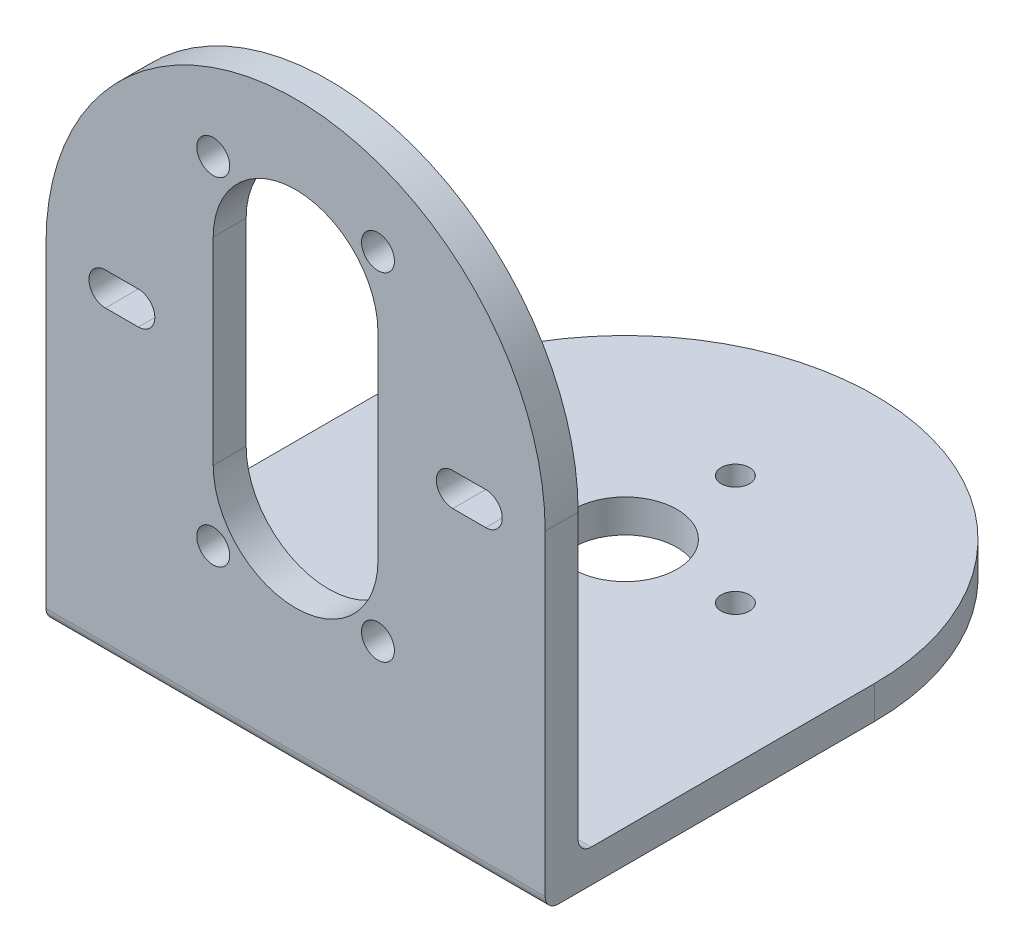
SolidWorks part; units mm, degrees
material "1060 Alloy"
ref_plane "Front" through (0, 0, 0) normal (0, 0, 1) x (1, 0, 0)
ref_plane "Top" through (0, 0, 0) normal (0, 1, 0) x (1, 0, 0)
ref_plane "Right" through (0, 0, 0) normal (1, 0, 0) x (0, 0, -1)
sketch "Sketch1" plane through (0, 0, 0) normal (0, 1, 0) x (1, 0, 0)
  line L0 (-19.24, 0) -> (-19.24, -25.4)
  line L1 (19.24, 0) -> (19.24, -25.4)
  line L2 (19.24, -25.4) -> (-19.24, -25.4)
  arc A0 (19.24, 0) -> (-19.24, 0) centre (0, 0) ccw
  circle A1 centre (0, 0) radius 4
  dimension "D1" = 38.48
  dimension "D2" = 8
  dimension "D3" = 25.4
extrude "Boss-Extrude1" add sketch "Sketch1" along normal blind 2.54
ref_plane "Plane1" through (0, 2.54, 0) normal (0, 1, 0) x (1, 0, 0)
sketch "Sketch2" plane through (0, 2.54, 0) normal (0, 1, 0) x (1, 0, 0)
  line L0 (-19.24, -25.4) -> (19.24, -25.4) construction
  circle A0 centre (0, 8.5) radius 1.09
  circle A1 centre (0, 0) radius 4 construction
  dimension "D1" = 2.18
  dimension "D2" = 8.5
  dimension "D3" = 33.9
extrude "Cut-Extrude1" cut sketch "Sketch2" against normal mid plane 10
pattern_circular "CirPattern1" count 4 over 360 about axis through (0, 2.54, 0) along (0, -1, 0) of "Cut-Extrude1"
ref_plane "Plane2" through (0, 0, 25.4) normal (0, 0, 1) x (1, 0, 0)
sketch "Sketch3" plane through (0, 0, 25.4) normal (0, 0, 1) x (1, 0, 0)
  line L0 (19.24, 2.54) -> (19.24, 25.4)
  line L1 (21.164, 2.54) -> (-21.164, 2.54) construction
  line L2 (19.24, 2.54) -> (19.24, 0) construction
  line L3 (-19.24, 2.54) -> (-19.24, 25.4)
  line L4 (0, 44.64) -> (0, 0) construction
  line L5 (6.35, 32.24) -> (6.35, 17)
  line L6 (-6.35, 32.24) -> (-6.35, 17)
  line L7 (6.35, 37.62) -> (6.35, 11.62) construction
  line L8 (6.35, 24.62) -> (-6.35, 24.62) construction
  line L9 (14.66, 25.89) -> (12.12, 25.89)
  line L10 (14.66, 23.35) -> (12.12, 23.35)
  line L11 (-14.66, 23.35) -> (-12.12, 23.35)
  line L12 (-14.66, 25.89) -> (-12.12, 25.89)
  line L13 (19.24, 2.54) -> (-19.24, 2.54)
  arc A0 (19.24, 25.4) -> (-19.24, 25.4) centre (0, 25.4) ccw
  arc A1 (6.35, 32.24) -> (-6.35, 32.24) centre (0, 32.24) ccw
  arc A2 (6.35, 17) -> (-6.35, 17) centre (0, 17) cw
  circle A3 centre (6.35, 37.62) radius 1.27
  circle A4 centre (6.35, 11.62) radius 1.27
  circle A5 centre (-6.35, 11.62) radius 1.27
  circle A6 centre (-6.35, 37.62) radius 1.27
  arc A7 (12.12, 25.89) -> (12.12, 23.35) centre (12.12, 24.62) ccw
  arc A8 (14.66, 25.89) -> (14.66, 23.35) centre (14.66, 24.62) cw
  arc A9 (-14.66, 25.89) -> (-14.66, 23.35) centre (-14.66, 24.62) ccw
  arc A10 (-12.12, 25.89) -> (-12.12, 23.35) centre (-12.12, 24.62) cw
  point P25 (6.35, 24.62)
  point P36 (10.85, 24.62)
  point P43 (-10.85, 24.62)
  dimension "D5" = 2.54
  dimension "D1" = 22.86
  dimension "D2" = 15.24
  dimension "D3" = 12.7
  dimension "D4" = 17
  dimension "D6" = 26
  dimension "D7" = 2.54
  dimension "D8" = 2.54
  dimension "D9" = 4.5
extrude "Boss-Extrude2" add sketch "Sketch3" against normal blind 2.54
fillet "Fillet1" radius 1 2 edges at (0, 0, 25.4)
